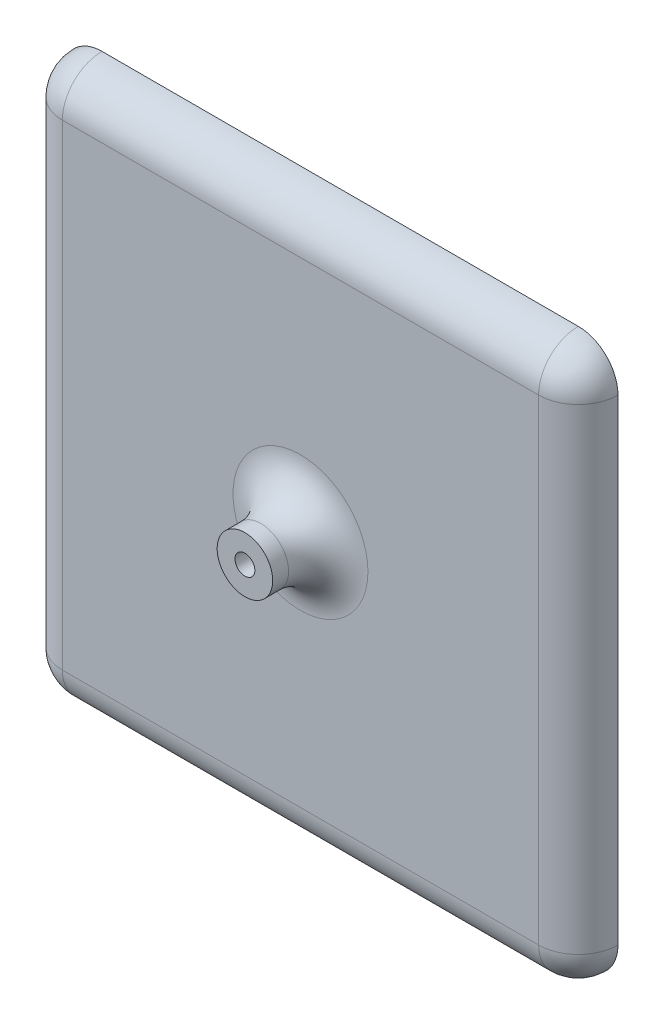
SolidWorks part; units mm, degrees
ref_plane "Plano frontal" through (0, 0, 0) normal (0, 0, 1) x (1, 0, 0)
ref_plane "Plano superior" through (0, 0, 0) normal (0, 1, 0) x (1, 0, 0)
ref_plane "Plano direito" through (0, 0, 0) normal (1, 0, 0) x (0, 0, -1)
sketch "Esboço1" plane through (0, 0, 0) normal (0, 0, 1) x (1, 0, 0)
  line L0 (0, 0) -> (104.1306, 0) construction
  line L1 (104.1306, 0) -> (104.1306, 140) construction
  line L2 (104.1306, 140) -> (-35.8694, 140) construction
  line L3 (-35.8694, 140) -> (-35.8694, 0) construction
  line L4 (-35.8694, 0) -> (0, 0) construction
  line L5 (-35.8694, 140) -> (104.1306, 0) construction
  line L6 (-35.8694, 140) -> (104.1306, 140)
  line L7 (-35.8694, 140) -> (-35.8694, 0)
  line L8 (-35.8694, 0) -> (104.1306, 0)
  line L9 (104.1306, 140) -> (104.1306, 0)
  line L10 (104.1306, 140) -> (-35.8694, 0) construction
  circle A0 centre (34.1306, 70) radius 2.5
  dimension "D3" = 5
  dimension "D1" = 140
  dimension "D2" = 140
extrude "Ressalto-extrusão1" add sketch "Esboço1" along normal blind 10
sketch "Esboço2" plane through (0, 0, 0) normal (0, 0, 1) x (1, 0, 0)
  circle A0 centre (34.1306, 70) radius 2.5
  circle A1 centre (34.1306, 70) radius 7
  dimension "D1" = 14
  dimension "D2" = 5
extrude "Ressalto-extrusão2" add sketch "Esboço2" along normal blind 24
fillet "Filete1" radius 10 1 edges at (34.1306, 0, 10)
fillet "Filete2" radius 10 1 edges at (34.1306, 140, 10)
fillet "Filete3" radius 10 3 edges at (-35.8694, 137.0711, 7.0711) (-35.8694, 2.9289, 7.0711) (-35.8694, 70, 10)
fillet "Filete4" radius 10 3 edges at (104.1306, 2.9289, 7.0711) (104.1306, 137.0711, 7.0711) (104.1306, 70, 10)
fillet "Filete5" radius 10 1 edges at (41.1306, 70, 10)
